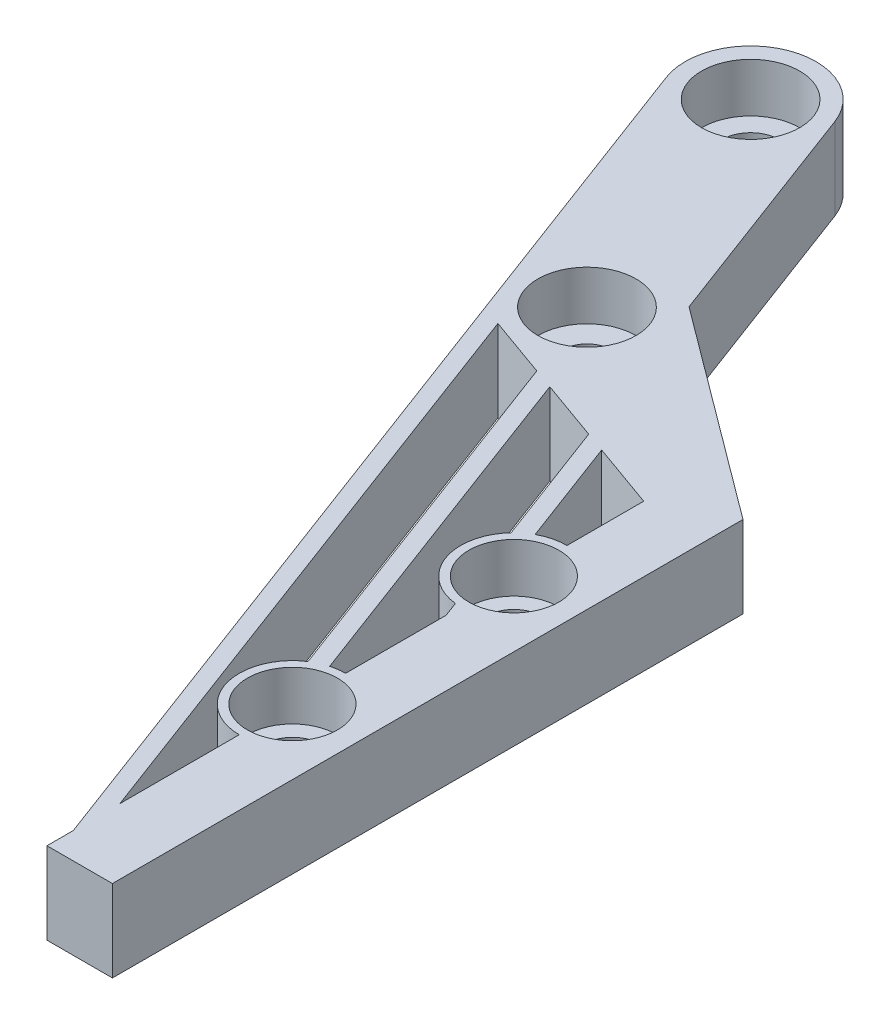
SolidWorks part; units mm, degrees
ref_plane "Ebene vorne" through (0, 0, 0) normal (0, 0, 1) x (1, 0, 0)
ref_plane "Ebene oben" through (0, 0, 0) normal (0, 1, 0) x (1, 0, 0)
ref_plane "Ebene rechts" through (0, 0, 0) normal (1, 0, 0) x (0, 0, -1)
sketch "Skizze1" plane through (0, 0, 0) normal (0, 1, 0) x (1, 0, 0)
  line L0 (0, 0) -> (6, -16) construction
  line L1 (0, 0) -> (6, 0) construction
  line L2 (6, 0) -> (6, -16) construction
  line L3 (-3.7453, -1.4045) -> (2.9065, -19.1426)
  line L4 (3.7453, 1.4045) -> (9.0935, -12.8574)
  line L8 (9.0935, -12.8574) -> (22, -17.4668)
  line L9 (2.9065, -19.1426) -> (18, -24.5332)
  line L10 (18, -24.5332) -> (18, -61)
  line L11 (18, -61) -> (22, -61)
  line L12 (22, -17.4668) -> (22, -61)
  line L13 (6, -16) -> (20, -21) construction
  line L14 (20, -21) -> (20, -61) construction
  arc A0 (3.7453, 1.4045) -> (-3.7453, -1.4045) centre (0, 0) ccw
  circle A1 centre (0, 0) radius 1.75
  circle A2 centre (6, -16) radius 1.5
  dimension "D4" = 3.5
  dimension "D5" = 3
  dimension "D1" = 6
  dimension "D2" = 16
  dimension "D3" = 8
  dimension "D6" = 8
  dimension "D7" = 5
  dimension "D8" = 4
  dimension "D9" = 14
  dimension "D10" = 40
extrude "Aufsatz-Linear austragen1" add sketch "Skizze1" along normal blind 5
sketch "Skizze2" plane through (0, 5, 0) normal (0, 1, 0) x (1, 0, 0)
  line L0 (2.9065, -19.1426) -> (18, -59.392)
  line L1 (18, -24.5332) -> (18, -61) construction
  line L2 (-3.7453, -1.4045) -> (2.9065, -19.1426) construction
  line L3 (2.9065, -19.1426) -> (4.1396, -19.583)
  line L4 (2.9065, -19.1426) -> (18, -24.5332) construction
  line L5 (4.1396, -19.583) -> (18, -56.544)
  line L6 (18, -56.544) -> (18, -59.392)
  line L7 (7.8391, -20.9043) -> (18, -48)
  line L8 (18, -48) -> (18, -45.152)
  line L9 (18, -45.152) -> (9.0723, -21.3447)
  line L10 (9.0723, -21.3447) -> (7.8391, -20.9043)
  line L11 (12.7717, -22.6659) -> (18, -36.608)
  line L12 (18, -36.608) -> (18, -33.76)
  line L13 (18, -33.76) -> (14.0049, -23.1063)
  line L14 (14.0049, -23.1063) -> (12.7717, -22.6659)
  dimension "D1" = 1
  dimension "D2" = 1
  dimension "D3" = 3
  dimension "D4" = 3
  dimension "D5" = 1
extrude "Aufsatz-Linear austragen2" add sketch "Skizze2" against normal up to surface (5 mm away) up to face at (11.3244, 0, 24.0318)
sketch "Skizze4" plane through (0, 5, 0) normal (0, 1, 0) x (1, 0, 0)
  line L0 (18, -24.5332) -> (18, -33.76) construction
  line L2 (18, -48) -> (18, -56.544) construction
  line L3 (18, -61) -> (22, -61) construction
  circle A0 centre (18, -32.4668) radius 3.25
  circle A2 centre (18, -46) radius 3.25
  dimension "D2" = 15
  dimension "D3" = 6.5
  dimension "D4" = 6.5
  dimension "D1" = 15
extrude "Aufsatz-Linear austragen3" add sketch "Skizze4" against normal up to surface (5 mm away) up to face at (16.6683, 0, 27.1332)
sketch "Skizze5" plane through (0, 5, 0) normal (0, 1, 0) x (1, 0, 0)
  circle A0 centre (18, -32.4668) radius 1.75
  arc A1 (18, -29.2168) -> (16.4449, -29.613) centre (18, -32.4668) ccw construction
  circle A2 centre (18, -46) radius 1.75
  arc A3 (18, -42.75) -> (17.1424, -42.8652) centre (18, -46) ccw construction
  dimension "D1" = 3.5
  dimension "D2" = 3.5
extrude "Schnitt-Linear austragen2" cut sketch "Skizze5" against normal up to surface (5 mm away) up to face at (12.3954, 0, 38.0436)
sketch "Skizze3" plane through (0, 5, 0) normal (0, 1, 0) x (1, 0, 0)
  circle A0 centre (0, 0) radius 3
  circle A1 centre (6, -16) radius 3
  circle A2 centre (18, -32.4668) radius 2.75
  circle A3 centre (18, -46) radius 2.75
  dimension "D1" = 6
  dimension "D2" = 6
  dimension "D3" = 5.5
  dimension "D4" = 5.5
extrude "Schnitt-Linear austragen1" cut sketch "Skizze3" against normal blind 3
sketch "Skizze6" plane through (0, 5, 0) normal (0, 1, 0) x (1, 0, 0)
  line L0 (9.0935, -12.8574) -> (22, -22.4668)
  line L1 (22, -61) -> (22, -17.4668) construction
  line L2 (22, -22.4668) -> (22, -17.4668)
  line L3 (22, -17.4668) -> (9.0935, -12.8574)
  dimension "D1" = 5
extrude "Schnitt-Linear austragen3" cut sketch "Skizze6" against normal up to surface (5 mm away) up to face at (18, 0, 34.2168)
